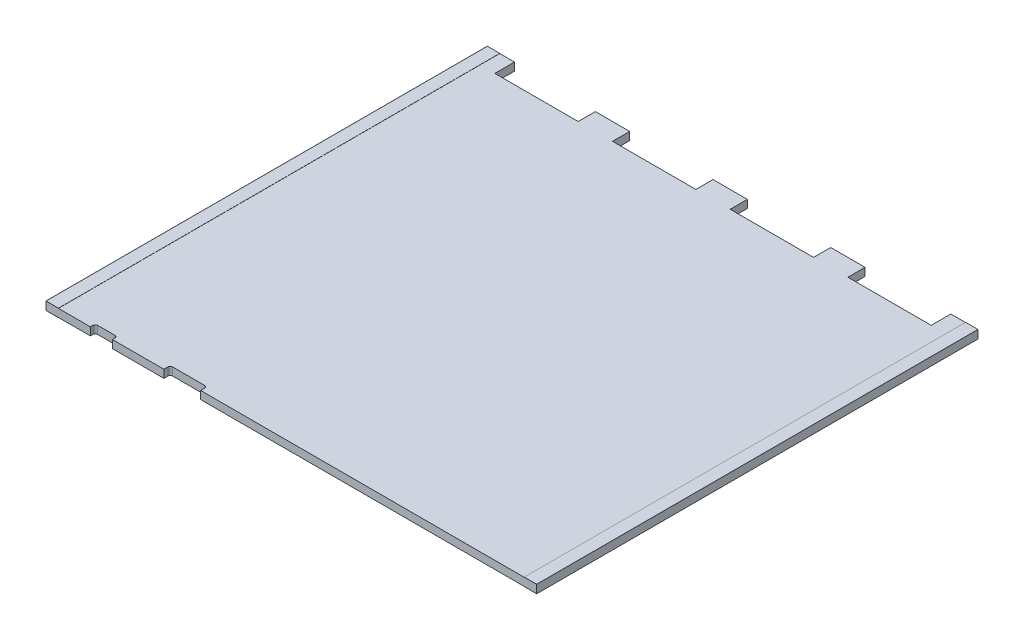
SolidWorks part; units mm, degrees
ref_plane "Front Plane" through (0, 0, 0) normal (0, 0, 1) x (1, 0, 0)
ref_plane "Top Plane" through (0, 0, 0) normal (0, 1, 0) x (1, 0, 0)
ref_plane "Right Plane" through (0, 0, 0) normal (1, 0, 0) x (0, 0, -1)
sketch "Sketch1" plane through (0, 0, 0) normal (0, 1, 0) x (1, 0, 0)
  line L0 (9, 0) -> (9, 0.5)
  line L1 (0, 0) -> (9, 0)
  line L2 (0, 0) -> (0, 90)
  line L3 (0, 90) -> (5.5, 90)
  line L4 (100, 0) -> (100, 90)
  line L5 (9.5, 1) -> (13, 1)
  line L6 (13.5, 0.5) -> (13.5, 0)
  line L7 (13.5, 0) -> (24, 0)
  line L8 (9.5, 0.5) -> (9, 0.5) construction
  line L9 (13, 1) -> (13, 0.5) construction
  line L10 (9.5, 1) -> (9.5, 0.5) construction
  line L11 (13.5, 0.5) -> (13, 0.5) construction
  line L12 (24, 0) -> (24, 0.8)
  line L13 (31.5, 0) -> (100, 0)
  line L14 (24, 0.8) -> (24.5, 0.8) construction
  line L15 (24.5, 0.8) -> (24.5, 1.3) construction
  line L16 (24.5, 1.3) -> (31, 1.3)
  line L17 (31, 1.3) -> (31, 0.8) construction
  line L18 (31, 0.8) -> (31.5, 0.8) construction
  line L19 (31.5, 0.8) -> (31.5, 0)
  line L20 (5.5, 90) -> (5.5, 86)
  line L21 (70.5, 89.5) -> (77.5, 89.5)
  line L22 (5.5, 86) -> (22.5, 86)
  line L23 (70.5, 86) -> (70.5, 89.5)
  line L24 (22.5, 86) -> (22.5, 89.5)
  line L25 (53.5, 86) -> (70.5, 86)
  line L26 (53.5, 89.5) -> (53.5, 86)
  line L27 (22.5, 89.5) -> (29.5, 89.5)
  line L28 (29.5, 89.5) -> (29.5, 86)
  line L29 (29.5, 86) -> (46.5, 86)
  line L30 (46.5, 86) -> (46.5, 89.5)
  line L31 (46.5, 89.5) -> (53.5, 89.5)
  line L32 (77.5, 89.5) -> (77.5, 86)
  line L33 (77.5, 86) -> (94.5, 86)
  line L34 (94.5, 86) -> (94.5, 90)
  line L35 (94.5, 90) -> (100, 90)
  arc A0 (9, 0.5) -> (9.5, 1) centre (9.5, 0.5) cw
  arc A1 (13, 1) -> (13.5, 0.5) centre (13, 0.5) cw
  arc A2 (24, 0.8) -> (24.5, 1.3) centre (24.5, 0.8) cw
  arc A3 (31, 1.3) -> (31.5, 0.8) centre (31, 0.8) cw
extrude "FR4" add sketch "Sketch1" along normal blind 1.6154
sketch "Sketch2" plane through (0, 1.6154, 0) normal (0, 1, 0) x (1, 0, 0)
  line L1 (0, 90) -> (2.5, 90)
  line L2 (0, 90) -> (0, 0)
  line L3 (0, 0) -> (2.5, 0)
  line L4 (2.5, 90) -> (2.5, 0)
  line L5 (31.5, 0) -> (100, 0) construction
  line L6 (100, 90) -> (97.5, 90)
  line L7 (100, 90) -> (100, 0)
  line L8 (100, 0) -> (97.5, 0)
  line L9 (97.5, 90) -> (97.5, 0)
extrude "top-plating" add sketch "Sketch2" along normal blind 0.0356 separate body
sketch "Sketch3" plane through (0, 0, 0) normal (0, -1, 0) x (1, 0, 0)
  line L0 (5.5, -90) -> (0, -90) construction
  line L1 (0, 0) -> (2.5, 0)
  line L2 (0, 0) -> (0, -90)
  line L3 (0, -90) -> (2.5, -90)
  line L4 (2.5, 0) -> (2.5, -90)
  line L6 (100, 0) -> (97.5, 0)
  line L7 (100, 0) -> (100, -90)
  line L8 (100, -90) -> (97.5, -90)
  line L9 (97.5, 0) -> (97.5, -90)
extrude "bottom-plating" add sketch "Sketch3" along normal blind 0.0356 separate body
sketch "Sketch4" plane through (0, 0, 0) normal (-1, 0, 0) x (0, 0, 1)
  line L1 (-90, -0.0356) -> (0, -0.0356)
  line L2 (-90, -0.0356) -> (-90, 1.651)
  line L3 (-90, 1.651) -> (0, 1.651)
  line L4 (0, -0.0356) -> (0, 1.651)
extrude "left-plating" add sketch "Sketch4" along normal blind 0.0356 separate body
sketch "Sketch5" plane through (100, 0, 0) normal (1, 0, 0) x (0, 0, -1)
  line L1 (90, 1.651) -> (0, 1.651)
  line L2 (90, 1.651) -> (90, -0.0356)
  line L3 (90, -0.0356) -> (0, -0.0356)
  line L4 (0, 1.651) -> (0, -0.0356)
extrude "right-plating" add sketch "Sketch5" along normal blind 0.0356 separate body
